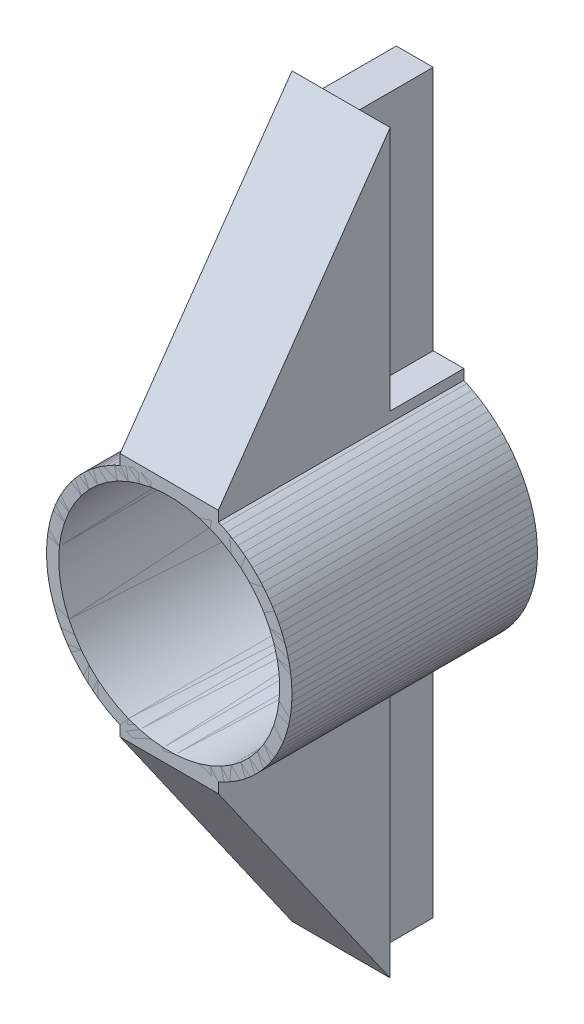
SolidWorks part; units mm, degrees
ref_plane "Front Plane" through (0, 0, 0) normal (0, 0, 1) x (1, 0, 0)
ref_plane "Top Plane" through (0, 0, 0) normal (0, 1, 0) x (1, 0, 0)
ref_plane "Right Plane" through (0, 0, 0) normal (1, 0, 0) x (0, 0, -1)
other "Configuration Table"
sketch "Sketch1" plane through (0, 0, 0) normal (0, 0, 1) x (1, 0, 0)
  circle A0 centre (0, 0) radius 9
  circle A1 centre (0, 0) radius 10
  dimension "D1" = 18
  dimension "D2" = 20
extrude "Boss-Extrude1" add sketch "Sketch1" along normal blind 20
sketch "Sketch2" plane through (0, 0, 0) normal (1, 0, 0) x (0, 0, -1)
  line L0 (-20, 10) -> (-20, 6.5)
  line L2 (-20, 6.5) -> (0, 6.5)
  line L3 (-20, 10) -> (-20, -10) construction
  line L5 (0, 6.5) -> (0, 30)
  line L6 (-20, 10) -> (-6, 30)
  line L7 (-6, 30) -> (0, 30)
  point P0 (-20, 10)
  dimension "D1" = 30
  dimension "D2" = 6
  dimension "D3" = 10
extrude "Boss-Extrude2" add sketch "Sketch2" along normal mid plane 8
sketch "Sketch3" plane through (0, 30, 0) normal (0, 1, 0) x (1, 0, 0)
  line L0 (-4, 0) -> (-1.5, 0)
  line L1 (4, 0) -> (-4, 0) construction
  line L2 (-1.5, 0) -> (-1.5, -6)
  line L3 (4, -6) -> (-4, -6) construction
  line L4 (-1.5, -6) -> (-4, -6)
  line L5 (-4, -6) -> (-4, 0)
  line L6 (4, 0) -> (1.5, 0)
  line L7 (1.5, 0) -> (1.5, -6)
  line L8 (1.5, -6) -> (4, -6)
  line L9 (4, -6) -> (4, 0)
  dimension "D1" = 2.5
extrude "Cut-Extrude1" cut sketch "Sketch3" against normal up to vertex (20 mm away) up to point (4, 10, 20)
move or copy body "Body-Move/Copy1" bodies to move or copy 104 copy yes number of copies 1 rotation origin (0, 0, 0) rotation axis (0, 0, 1) rotation angle 180
sketch "Sketch4" plane through (0, 0, 0) normal (0, 0, -1) x (-1, 0, 0)
  circle A0 centre (0, 0) radius 9
extrude "Cut-Extrude2" cut sketch "Sketch4" against normal through all
